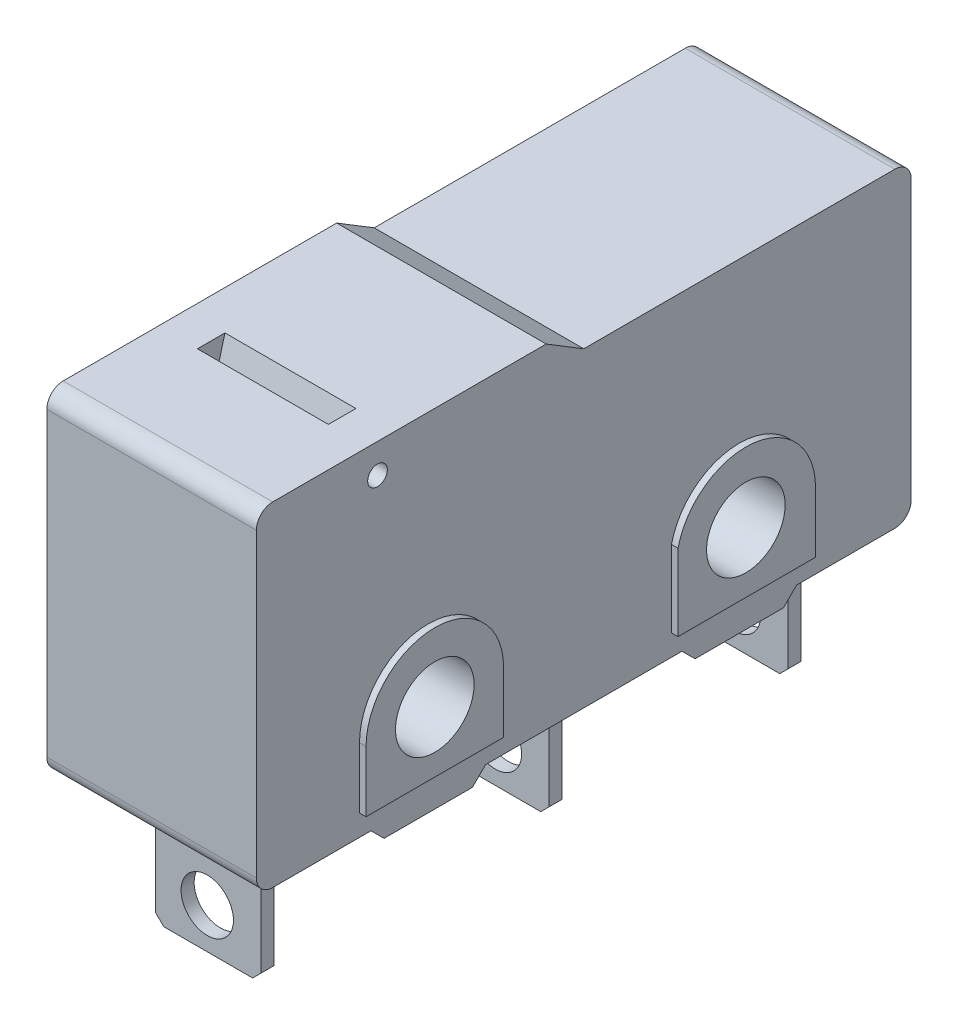
SolidWorks part; units mm, degrees
ref_plane "Front Plane" through (0, 0, 0) normal (0, 0, 1) x (1, 0, 0)
ref_plane "Top Plane" through (0, 0, 0) normal (0, 1, 0) x (1, 0, 0)
ref_plane "Right Plane" through (0, 0, 0) normal (1, 0, 0) x (0, 0, -1)
sketch "Sketch1" plane through (0, 0, 0) normal (1, 0, 0) x (0, 0, -1)
  line L0 (10, 4.4) -> (0, 4.4)
  line L2 (10, 4.4) -> (10, -5.1)
  line L4 (-10, 5.1) -> (-10, -5.1)
  line L5 (0, 4.4) -> (-1.1476, 5.1)
  line L6 (10, -5.1) -> (-10, 5.1) construction
  line L7 (-1.1476, 5.1) -> (-10, 5.1)
  line L8 (-10, -5.1) -> (-6.5, -5.1)
  line L12 (-3, -5.1) -> (3, -5.1)
  line L16 (6.5, -5.1) -> (10, -5.1)
  line L17 (-6.5, -5.1) -> (-6.1, -5.5)
  line L18 (-6.1, -5.5) -> (-3.4, -5.5)
  line L19 (-3.4, -5.5) -> (-3, -5.1)
  line L20 (6.5, -5.1) -> (6.1, -5.5)
  line L21 (3, -5.1) -> (3.4, -5.5)
  line L23 (3.4, -5.5) -> (6.1, -5.5)
  point P0 (0, 0)
  dimension "D1" = 20
  dimension "D2" = 10.2
  dimension "D3" = 9.5
  dimension "D4" = 20
  dimension "D5" = 3.5
  dimension "D6" = 0.4
  dimension "D7" = 45
  dimension "D8" = 45
  dimension "D9" = 45
  dimension "D10" = 0.4
  dimension "D11" = 45
  dimension "D12" = 6
extrude "Boss-Extrude1" add sketch "Sketch1" along normal mid plane 6.4
sketch "Sketch5" plane through (0, -5.1, 0) normal (0, -1, 0) x (1, 0, 0)
  line L0 (-1.5777, 8.3) -> (1.6361, 8.3)
  line L1 (1.6361, 8.3) -> (1.6361, 7.9)
  line L2 (1.6361, 7.9) -> (-1.5777, 7.9)
  line L3 (-1.5777, 7.9) -> (-1.5777, 8.3)
  line L4 (-1.5777, -0.5) -> (1.6361, -0.5)
  line L5 (1.6361, -0.5) -> (1.6361, -0.9)
  line L6 (1.6361, -0.9) -> (-1.5777, -0.9)
  line L7 (-1.5777, -0.9) -> (-1.5777, -0.5)
  line L8 (-1.5777, -7.8) -> (1.6361, -7.8)
  line L9 (1.6361, -7.8) -> (1.6361, -8.2)
  line L10 (1.6361, -8.2) -> (-1.5777, -8.2)
  line L11 (-1.5777, -8.2) -> (-1.5777, -7.8)
  line L12 (3.2, 10) -> (-3.2, 10) construction
  dimension "D1" = 1.7
  dimension "D2" = 0.4
  dimension "D3" = 8.8
  dimension "D4" = 7.3
extrude "Boss-Extrude2" add sketch "Sketch5" along normal blind 3.9
chamfer "Chamfer2" distance 0.25 angle 45 6 edges at (-1.5777, -9, 8.1) (1.6361, -9, -8) (-1.5777, -9, -8) (1.6361, -9, -0.7) (-1.5777, -9, -0.7) (1.6361, -9, 8.1)
sketch "Sketch6" plane through (0, 0, 8.3) normal (0, 0, 1) x (1, 0, 0)
  line L0 (0, -55) -> (0, 55) construction
  circle A0 centre (0, -7.7687) radius 0.8
  dimension "D1" = 1.6
extrude "Cut-Extrude1" cut sketch "Sketch6" against normal through all
fillet "Fillet1" radius 0.5 4 edges at (0, -5.1, -10) (0, 4.4, -10) (0, -5.1, 10) (0, 5.1, 10)
sketch "Sketch7" plane through (3.2, 0, 0) normal (1, 0, 0) x (0, 0, -1)
  line L0 (-10, 4.6) -> (-10, -4.6) construction
  line L1 (-9.5, -5.1) -> (-6.5, -5.1) construction
  circle A0 centre (-4.75, -2.6) radius 1.2
  circle A1 centre (4.75, -2.6) radius 1.2
  dimension "D3" = 2.4
  dimension "D1" = 5.25
  dimension "D2" = 9.5
  dimension "D4" = 2.5
extrude "Cut-Extrude2" cut sketch "Sketch7" against normal through all
sketch "Sketch11" plane through (0, 0, 0) normal (1, 0, 0) x (0, 0, -1)
  line L0 (-6.85, -4.4534) -> (-2.65, -4.4534)
  line L1 (-2.65, -4.4534) -> (-2.65, -2.6)
  line L2 (-6.85, -2.6) -> (-6.85, -4.4534)
  line L3 (2.6782, -4.4534) -> (6.8782, -4.4534)
  line L4 (6.8782, -4.4534) -> (6.8782, -2.6)
  line L5 (2.6782, -2.1134) -> (2.6782, -4.4534)
  circle A0 centre (-4.75, -2.6) radius 1.2
  circle A1 centre (4.75, -2.6) radius 1.2
  arc A2 (-2.65, -2.6) -> (-6.85, -2.6) centre (-4.75, -2.6) ccw
  arc A3 (6.8782, -2.6) -> (2.6782, -2.1134) centre (4.75, -2.6) ccw
  dimension "D1" = 4.2
extrude "Boss-Extrude5" add sketch "Sketch11" along normal blind 3.4 and the other way blind 3.4
sketch "Sketch12" plane through (3.2, 0, 0) normal (1, 0, 0) x (0, 0, -1)
  line L0 (10, -4.6) -> (10, 3.9) construction
  circle A0 centre (-6.3, 4.202) radius 0.3
  dimension "D1" = 0.6
  dimension "D2" = 16.3
extrude "Cut-Extrude3" cut sketch "Sketch12" against normal through all
sketch "Sketch13" plane through (0, 0, 0) normal (1, 0, 0) x (0, 0, -1)
  line L0 (-6.6, 4.202) -> (-6.6, 5.1)
  line L1 (-1.1476, 5.1) -> (-9.5, 5.1) construction
  line L2 (-6.6, 5.1) -> (-5.7594, 5.1)
  line L3 (-5.7594, 5.1) -> (-6, 4.202)
  line L4 (-6, 4.202) -> (-6.6, 4.202)
  circle A0 centre (-6.3, 4.202) radius 0.3 construction
  dimension "D1" = 75
extrude "Cut-Extrude4" cut sketch "Sketch13" against normal blind 2 and the other way blind 2
